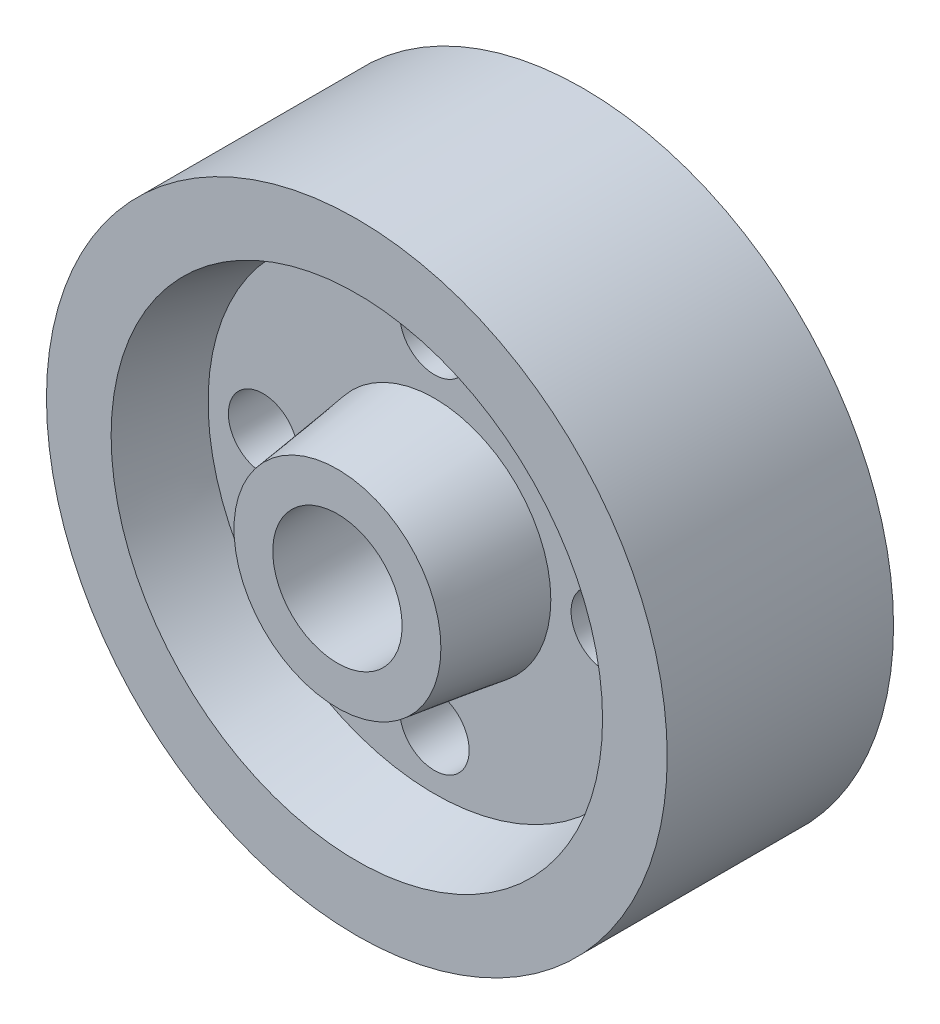
SolidWorks part; units mm, degrees
note: The reader was unsure of these and kept them because the rebuilt part matched: shared geometry of "Sketch3<4>".
ref_plane "Front Plane" through (0, 0, 0) normal (0, 0, 1) x (1, 0, 0)
ref_plane "Top Plane" through (0, 0, 0) normal (0, 1, 0) x (1, 0, 0)
ref_plane "Right Plane" through (0, 0, 0) normal (1, 0, 0) x (0, 0, -1)
sketch "Sketch1" plane through (0, 0, 0) normal (1, 0, 0) x (0, 0, -1)
  line L0 (0, 0) -> (41, 0)
  line L1 (41, 0) -> (41, 16)
  line L2 (41, 16) -> (26, 18)
  line L3 (26, 18) -> (26, 35)
  line L4 (26, 35) -> (38, 38)
  line L5 (38, 38) -> (38, 48)
  line L6 (38, 48) -> (3, 48)
  line L7 (3, 48) -> (3, 38)
  line L8 (3, 38) -> (15, 35)
  line L9 (15, 35) -> (15, 18)
  line L10 (15, 18) -> (0, 16)
  line L11 (0, 16) -> (0, 0)
  point P3 (0, 0)
  dimension "D1" = 41
  dimension "D2" = 16
  dimension "D3" = 18
  dimension "D4" = 18
  dimension "D5" = 35
  dimension "D6" = 11
  dimension "D7" = 35
  dimension "D8" = 38
  dimension "D9" = 3
  dimension "D10" = 10
revolve "Revolve1" add sketch "Sketch1" angle 360 about L0
sketch "Sketch2" plane through (0, 0, 0) normal (0, 0, 1) x (1, 0, 0)
  circle A0 centre (0, 0) radius 10
  dimension "D1" = 20
extrude "Cut-Extrude1" cut sketch "Sketch2" against normal up to next
sketch "Sketch3" plane through (0, 0, -15) normal (0, 0, 1) x (1, 0, 0)
  line L0 (-56.6306, 0) -> (53.5514, 0) construction
  line L1 (0, 51.8779) -> (0, -52.4134) construction
  circle A0 centre (0, 0) radius 26.5 construction
  circle A1 centre (0, 26.5) radius 5.3689
  circle A2 centre (26.5, 0) radius 5.3689
  circle A3 centre (0, -26.5) radius 5.3689
  circle A4 centre (-26.5, 0) radius 5.3689
  point P9 (29.0031, 2.8592)
  point P10 (30.4332, 6.7263)
  point P11 (27.1969, 0)
  point P18 (0, 0)
  dimension "D1" = 53
  dimension "D2" = 10.7378
  dimension "D3" = 4
extrude "Cut-Extrude2" cut sketch "Sketch3" against normal up to next contours A1
extrude "Cut-Extrude3" cut sketch "Sketch3<4>" against normal up to next (11 mm away)
sketch "Sketch3<4>" plane through (0, 0, -15) normal (0, 0, 1) x (1, 0, 0) same geometry as "Sketch3"
